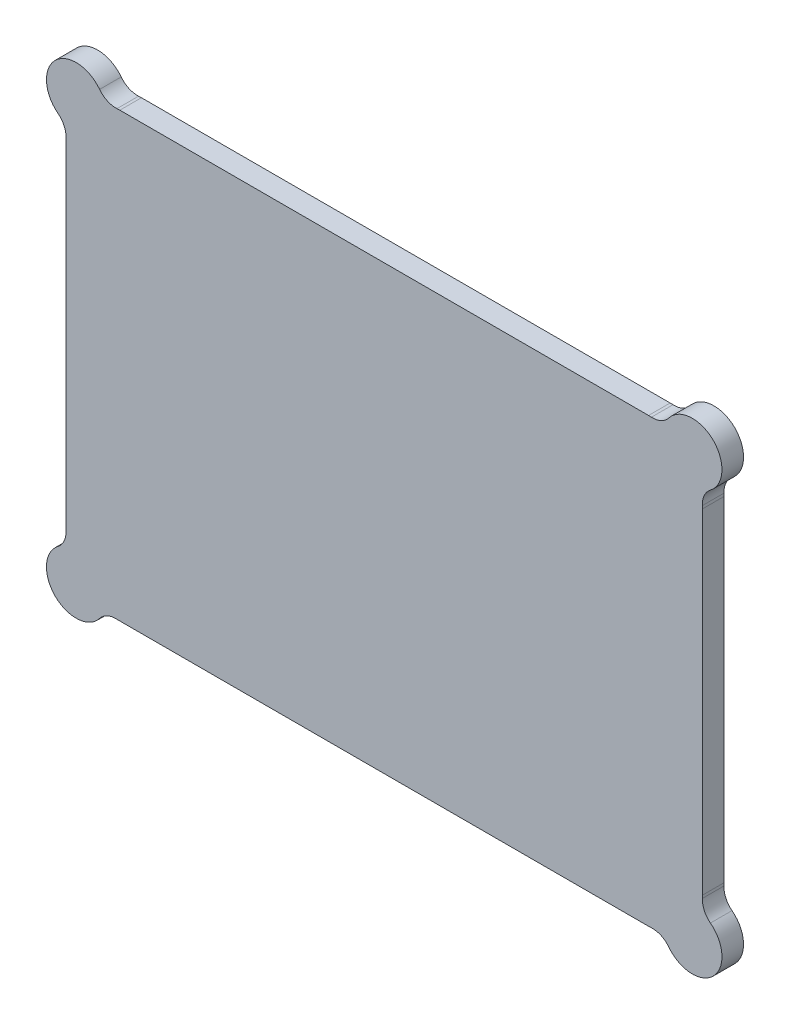
SolidWorks part; units mm, degrees
material "Custom Plastic"
ref_plane "X-Y Datum" through (0, 0, 0) normal (0, 0, 1) x (1, 0, 0)
ref_plane "X-Z Datum" through (0, 0, 0) normal (0, 1, 0) x (1, 0, 0)
ref_plane "Y-Z Datum" through (0, 0, 0) normal (1, 0, 0) x (0, 0, -1)
sketch "Sketch2" plane through (0, 0, 0) normal (0, 0, 1) x (1, 0, 0)
  line L4 (59, 41) -> (-59, 41)
  line L6 (59, 41) -> (-59, 41)
  line L20 (-60.27, -41) -> (60.27, -41)
  line L21 (-60.27, -41) -> (60.27, -41)
  line L22 (59, 40.8514) -> (59, 41)
  line L23 (59, 40.8514) -> (59, 41)
  line L33 (-59, 41) -> (-59, 40.8514)
  line L34 (-59, 41) -> (-59, 40.8514)
  line L35 (-59, 30.1486) -> (-59, -30.1486)
  line L37 (-59, 30.1486) -> (-59, -30.1486)
  line L41 (59, -30.1486) -> (59, 30.1486)
  line L42 (59, -30.1486) -> (59, 30.1486)
  line L57 (-59, 31) -> (-59, -31)
  line L61 (-49, -41) -> (49, -41)
  line L65 (59, -31) -> (59, 31)
  line L66 (49, 41) -> (-49, 41)
  arc A4 (59, 30.1486) -> (59, 40.8514) centre (60.27, 35.5) ccw
  arc A12 (59, 30.1486) -> (59, 40.8514) centre (60.27, 35.5) ccw
  arc A14 (-59, 40.8514) -> (-59, 30.1486) centre (-60.27, 35.5) ccw
  arc A26 (-59, 40.8514) -> (-59, 30.1486) centre (-60.27, 35.5) ccw
  arc A33 (-59, -30.1486) -> (-60.27, -41) centre (-60.27, -35.5) ccw
  arc A34 (-59, -30.1486) -> (-60.27, -41) centre (-60.27, -35.5) ccw
  arc A35 (60.27, -41) -> (59, -30.1486) centre (60.27, -35.5) ccw
  arc A36 (60.27, -41) -> (59, -30.1486) centre (60.27, -35.5) ccw
  arc A96 (-59, -31) -> (-58.9859, -31.5308) centre (-49, -31) ccw
  arc A97 (-60.4645, -34.7506) -> (-58.9859, -31.5308) centre (-62.7905, -31.7331) ccw
  arc A98 (-60.4645, -34.7506) -> (-52.7506, -42.4645) centre (-57.1066, -39.1066) ccw
  arc A99 (-49.5308, -40.9859) -> (-52.7506, -42.4645) centre (-49.7331, -44.7905) ccw
  arc A100 (-49.5308, -40.9859) -> (-49, -41) centre (-49, -31) ccw
  arc A101 (49, -41) -> (49.5308, -40.9859) centre (49, -31) ccw
  arc A102 (52.7506, -42.4645) -> (49.5308, -40.9859) centre (49.7331, -44.7905) ccw
  arc A103 (52.7506, -42.4645) -> (60.4645, -34.7506) centre (57.1066, -39.1066) ccw
  arc A104 (58.9859, -31.5308) -> (60.4645, -34.7506) centre (62.7905, -31.7331) ccw
  arc A105 (58.9859, -31.5308) -> (59, -31) centre (49, -31) ccw
  arc A106 (59, 31) -> (58.9859, 31.5308) centre (49, 31) ccw
  arc A107 (60.4645, 34.7506) -> (58.9859, 31.5308) centre (62.7905, 31.7331) ccw
  arc A108 (60.4645, 34.7506) -> (52.7506, 42.4645) centre (57.1066, 39.1066) ccw
  arc A109 (49.5308, 40.9859) -> (52.7506, 42.4645) centre (49.7331, 44.7905) ccw
  arc A110 (49.5308, 40.9859) -> (49, 41) centre (49, 31) ccw
  arc A111 (-49, 41) -> (-49.5308, 40.9859) centre (-49, 31) ccw
  arc A112 (-52.7506, 42.4645) -> (-49.5308, 40.9859) centre (-49.7331, 44.7905) ccw
  arc A113 (-52.7506, 42.4645) -> (-60.4645, 34.7506) centre (-57.1066, 39.1066) ccw
  arc A114 (-58.9859, 31.5308) -> (-60.4645, 34.7506) centre (-62.7905, 31.7331) ccw
  arc A115 (-58.9859, 31.5308) -> (-59, 31) centre (-49, 31) ccw
  dimension "D1" = 0
extrude "Boss-Extrude1" add sketch "Sketch2" along normal blind 4 contours L57 A96 A97 A98 A99 A100 L61 A101 A102 A103 A104 A105 L65 A106 A107 A108 A109 A110 L66 A111 A112 A113 A114 A115
